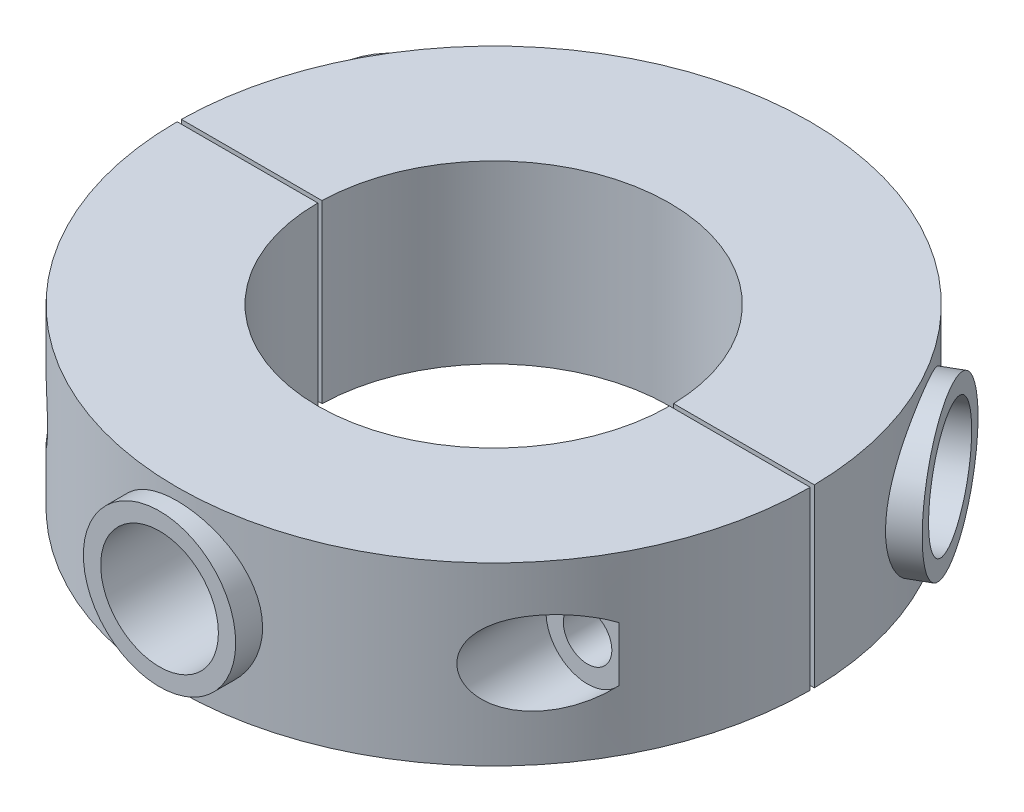
SolidWorks part; units mm, degrees
note: The reader was unsure of these and kept them because the rebuilt part matched: shared geometry of "Sketch5<3>", "Sketch6<3>".
ref_plane "Front Plane" through (0, 0, 0) normal (0, 0, 1) x (1, 0, 0)
ref_plane "Top Plane" through (0, 0, 0) normal (0, 1, 0) x (1, 0, 0)
ref_plane "Right Plane" through (0, 0, 0) normal (1, 0, 0) x (0, 0, -1)
sketch "Sketch1" plane through (0, 0, 0) normal (0, 1, 0) x (1, 0, 0)
  circle A0 centre (0, 0) radius 12.7
  circle A1 centre (0, 0) radius 22.86
  dimension "D1" = 25.4
  dimension "D2" = 45.72
extrude "Boss-Extrude1" add sketch "Sketch1" along normal blind 12.7 contours A1 A0
ref_plane "Plane1" through (0, 0, 24.13) normal (0, 0, 1) x (1, 0, 0)
sketch "Sketch4" plane through (0, 0, 24.13) normal (0, 0, 1) x (1, 0, 0)
  circle A0 centre (0, 6.35) radius 5.5
  point P0 (0, 6.35)
  dimension "D1" = 11
  dimension "D2" = 6.35
extrude "Boss-Extrude2" add sketch "Sketch4" against normal up to surface (1.9415 mm away) up to face at (0, 12.7, 22.86)
sketch "Sketch2" plane through (0, 0, 0) normal (0, 0, 1) x (1, 0, 0)
  circle A0 centre (0, 6.35) radius 4.25
  circle A1 centre (0, 6.35) radius 5.5 construction
  point P0 (0, 6.35)
  dimension "D1" = 8.5
extrude "Cut-Extrude3" cut sketch "Sketch2" along normal up to surface (6.35 mm away) from offset 17.78 up to face at (5.5, 6.35, 24.13)
pattern_circular "CirPattern1" count 3 over 360 about axis through (0, 0, 0) along (0, 1, 0) of "Boss-Extrude2", "Cut-Extrude3"
split "Split1" trim tools "Front Plane" bodies to split 104 resulting bodies 105 106
sketch "Sketch5" plane through (0, 0, 0) normal (0, 0, 1) x (1, 0, 0)
  line L0 (-22.86, 12.7) -> (-12.7, 12.7) construction
  line L1 (-22.86, 12.7) -> (-22.86, 0) construction
  line L2 (12.7, 12.7) -> (22.86, 12.7) construction
  line L3 (22.86, 12.7) -> (12.7, 12.7) construction
  line L5 (12.7, 0) -> (22.86, 0) construction
  line L6 (22.86, 0) -> (22.86, 12.7) construction
  line L7 (-12.7, 12.7) -> (-22.86, 12.7) construction
  line L8 (-22.86, 0) -> (-12.7, 0) construction
  line L10 (22.86, 12.7) -> (12.7, 12.7)
  line L12 (12.7, 0) -> (22.86, 0)
  line L13 (22.86, 0) -> (22.86, 12.7)
  line L14 (12.7, 12.7) -> (-22.86, 12.7)
  line L15 (-22.86, 12.7) -> (-22.86, 0)
  line L16 (-22.86, 0) -> (12.7, 0)
  circle A0 centre (-17.78, 6.35) radius 2.6
  circle A1 centre (17.78, 6.35) radius 2.6
  point P4 (-17.78, 12.7)
  point P7 (-22.86, 6.35)
  point P12 (17.78, 12.7)
  dimension "D1" = 5.2
extrude "Cut-Extrude4" cut sketch "Sketch5" against normal blind 4.2 contours A1 | A0
extrude "Cut-Extrude5" cut sketch "Sketch5<3>" against normal blind 0.3
sketch "Sketch5<3>" plane through (0, 0, 0) normal (0, 0, 1) x (1, 0, 0) same geometry as "Sketch5"
sketch "Sketch6" plane through (0, 0, 0) normal (0, 0, -1) x (-1, 0, 0)
  line L0 (-12.7, 12.7) -> (-22.86, 12.7) construction
  line L1 (-22.86, 0) -> (-22.86, 12.7) construction
  line L2 (22.86, 12.7) -> (12.7, 12.7) construction
  circle A0 centre (-17.78, 6.35) radius 1.75
  circle A1 centre (17.78, 6.35) radius 1.75
  circle A2 centre (-17.78, 6.35) radius 3
  circle A3 centre (17.78, 6.35) radius 3
  point P4 (-17.78, 12.7)
  point P7 (-22.86, 6.35)
  point P13 (17.78, 12.7)
  dimension "D1" = 3.5
  dimension "D2" = 6
extrude "Cut-Extrude6" cut sketch "Sketch6" against normal up to next contours A0 | A1
extrude "Cut-Extrude7" cut sketch "Sketch6<3>" against normal through all from offset 11 contours A3 | A2 offset against normal yes
sketch "Sketch6<3>" plane through (0, 0, 0) normal (0, 0, -1) x (-1, 0, 0) same geometry as "Sketch6"
